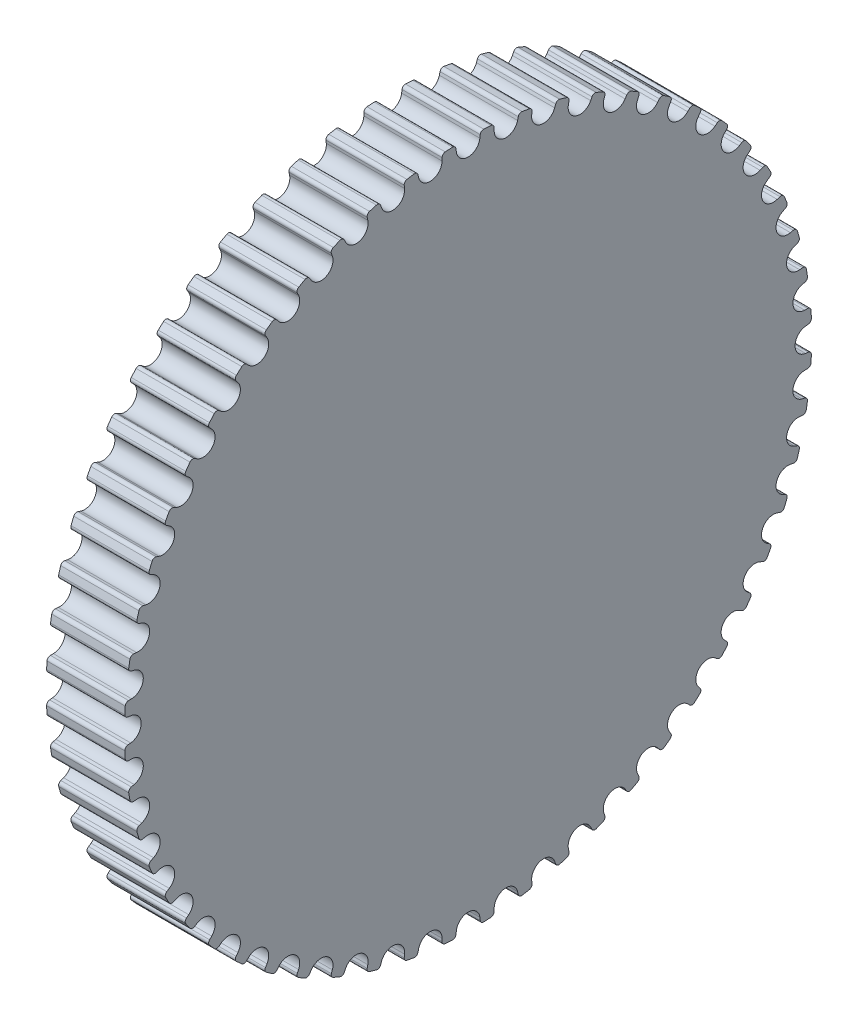
SolidWorks part; units mm, degrees
ref_plane "前视基准面" through (0, 0, 0) normal (0, 0, 1) x (1, 0, 0)
ref_plane "上视基准面" through (0, 0, 0) normal (0, 1, 0) x (1, 0, 0)
ref_plane "右视基准面" through (0, 0, 0) normal (1, 0, 0) x (0, 0, -1)
sketch "草图1" plane through (0, 0, 0) normal (0, 0, 1) x (1, 0, 0)
  line L0 (0, 0) -> (64.8368, 0) construction
  line L1 (0, 5.2718) -> (0, 26.359)
  line L2 (0, 26.359) -> (6, 26.359)
  line L3 (6, 26.359) -> (6, 10.5436)
  line L10 (6, 10.5436) -> (6, 0)
  line L11 (6, 0) -> (0, 0)
  line L12 (0, 0) -> (0, 5.2718)
  dimension "B" = 6
  dimension "da" = 52.718
revolve "旋转1" add sketch "草图1" angle 360 about L0
ref_axis "基准轴1" through (-0.45, 0, 0) along (1, 0, 0)
sketch "草图6" plane through (0, 0, 0) normal (1, 0, 0) x (0, 0, -1)
  line L0 (0, 0) -> (0, 30.6512) construction
  line L1 (0.9309, 26.1036) -> (0.9032, 25.8781)
  line L2 (1.4605, 26.3185) -> (1.6571, 27.9201)
  line L3 (-1.4605, 26.3185) -> (-1.6571, 27.9201)
  line L4 (-0.9309, 26.1036) -> (-0.9032, 25.8781)
  circle A0 centre (0, 0) radius 26.359 construction
  circle A1 centre (0, 0) radius 25.079 construction
  arc A2 (-0.9032, 25.8781) -> (0.9032, 25.8781) centre (0, 25.989) ccw
  arc A3 (1.6571, 27.9201) -> (-1.6571, 27.9201) centre (0, 0) ccw
  arc A4 (0.9309, 26.1036) -> (1.2008, 26.3316) centre (1.189, 26.0719) cw
  arc A5 (1.2008, 26.3316) -> (1.4605, 26.3185) centre (0, 0) cw
  arc A6 (-1.2008, 26.3316) -> (-1.4605, 26.3185) centre (0, 0) ccw
  arc A7 (-0.9309, 26.1036) -> (-1.2008, 26.3316) centre (-1.189, 26.0719) ccw
  point P7 (0, 1.9)
  point P8 (0, 29.3712)
  point P15 (0.9601, 26.3415)
  dimension "D1" = 50.158
  dimension "ra" = 0.26
  dimension "rf" = 0.91
  dimension "hg" = 1.28
  dimension "D3" = 0.26
  dimension "D4" = 1.6136
  dimension "angle" = 14
  dimension "bw" = 1.9
extrude "切除-拉伸2" cut sketch "草图6" along normal up to next
pattern_circular "阵列(圆周)3" count 56 over 360 about axis through (-0.45, 0, 0) along (1, 0, 0) of "切除-拉伸2"
equation "\"D1@草图6\" = \"da@草图1\"  - \"hg@草图6\" - \"hg@草图6\""
equation "\"D3@草图6\" = \"ra@草图6\""
